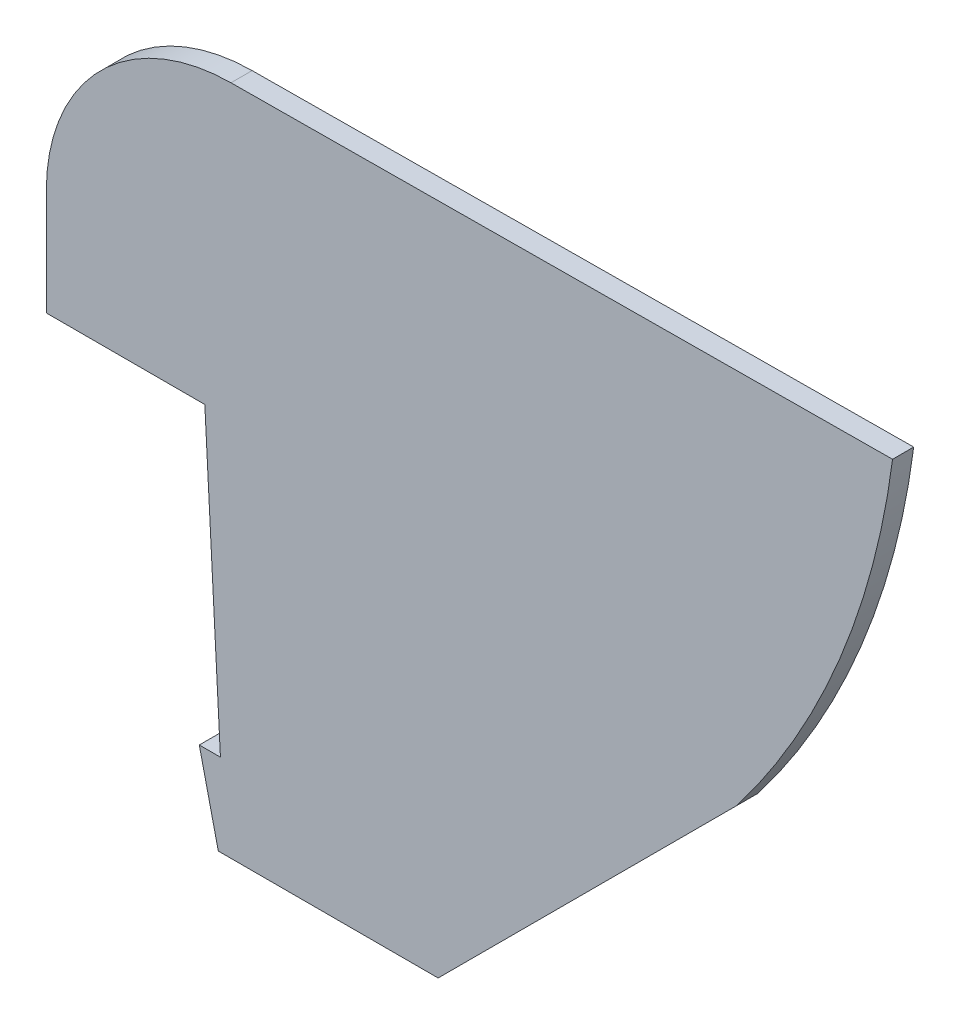
SolidWorks part; units mm, degrees
ref_plane "Plan de face" through (0, 0, 0) normal (0, 0, 1) x (1, 0, 0)
ref_plane "Plan de dessus" through (0, 0, 0) normal (0, 1, 0) x (1, 0, 0)
ref_plane "Plan de droite" through (0, 0, 0) normal (1, 0, 0) x (0, 0, -1)
sketch "Esquisse1" plane through (0, 0, 0) normal (0, 0, 1) x (1, 0, 0)
  line L0 (0, 0) -> (188.5, 0) construction
  line L1 (0, 0) -> (0, -25)
  line L2 (0, -25) -> (37.5, -25)
  line L3 (37.5, -25) -> (41.1897, -95.4034)
  line L4 (41.1897, -95.4034) -> (36.1897, -95.4034)
  line L5 (36.1897, -95.4034) -> (40.6887, -114.8908)
  line L6 (40.6887, -114.8908) -> (92.6887, -114.8908)
  line L7 (92.6887, -114.8908) -> (163.3994, -44.1801)
  line L8 (43.6829, 43.9989) -> (200.1829, 45.1267)
  arc A0 (0, 0) -> (43.6829, 43.9989) centre (44, 0) cw
  arc A1 (163.3994, -44.1801) -> (200.1829, 45.1267) centre (16.1609, 68.6928) ccw
  dimension "D11" = 44
  dimension "D1" = 188.5
  dimension "D2" = 25
  dimension "D3" = 37.5
  dimension "D4" = 93
  dimension "D5" = 70.5
  dimension "D6" = 5
  dimension "D7" = 20
  dimension "D8" = 52
  dimension "D9" = 135
  dimension "D10" = 100
  dimension "D12" = 156.5
extrude "Boss.-Extru.1" add sketch "Esquisse1" along normal blind 5
sketch "Esquisse2" plane through (0, 0, 5) normal (0, 0, 1) x (1, 0, 0)
  line L0 (0, 0) -> (188.5, 0)
  dimension "D1" = 188.5
